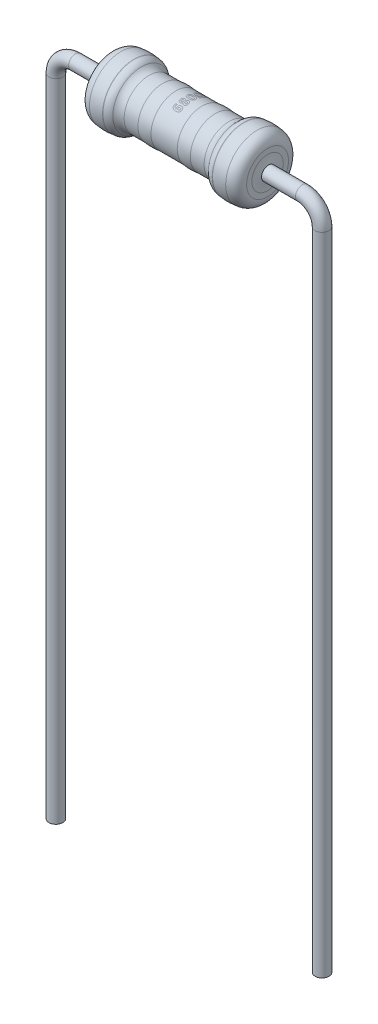
SolidWorks part; units mm, degrees
material "Plain Carbon Steel"
ref_plane "Front Plane" through (0, 0, 0) normal (0, 0, 1) x (1, 0, 0)
ref_plane "Top Plane" through (0, 0, 0) normal (0, 1, 0) x (1, 0, 0)
ref_plane "Right Plane" through (0, 0, 0) normal (1, 0, 0) x (0, 0, -1)
sketch "Sketch1" plane through (0, 0, 0) normal (0, 0, 1) x (1, 0, 0)
  line L0 (-4.33, 0) -> (4.33, 0)
  line L1 (-5.08, -0.75) -> (-5.08, -25.4)
  line L2 (5.08, -0.75) -> (5.08, -25.4)
  line L3 (-5.08, -25.4) -> (5.08, -25.4) construction
  line L4 (0, 0) -> (0, -25.4) construction
  arc A0 (-4.33, 0) -> (-5.08, -0.75) centre (-4.33, -0.75) ccw
  arc A1 (4.33, 0) -> (5.08, -0.75) centre (4.33, -0.75) cw
  dimension "D2" = 0.75
  dimension "D1" = 10.16
  dimension "D3" = 25.4
ref_plane "Plane1" through (-5.08, -25.4, 0) normal (0, -1, 0) x (-1, 0, 0)
sketch "Sketch2" plane through (-5.08, -25.4, 0) normal (0, -1, 0) x (-1, 0, 0)
  circle A0 centre (0, 0) radius 0.265
  dimension "D1" = 0.53
sweep "Sweep1" add profiles "Sketch2" path "Sketch1"
sketch "Sketch3" plane through (0, 0, 0) normal (0, 0, 1) x (1, 0, 0)
  line L0 (-3, 0) -> (3, 0)
  line L5 (-3, 0) -> (-3, 1.2)
  line L6 (3, 0) -> (3, 1.2)
  line L7 (-3, 1.2) -> (-1.75, 1.2)
  line L8 (3, 1.2) -> (1.75, 1.2)
  line L9 (-1.75, 1.2) -> (-1.75, 0.95)
  line L10 (-1.75, 0.95) -> (1.75, 0.95)
  line L11 (1.75, 0.95) -> (1.75, 1.2)
  line L12 (0, 0) -> (0, 0.95) construction
  dimension "D1" = 6
  dimension "D2" = 1.2
  dimension "D3" = 3.5
  dimension "D4" = 0.95
  dimension "D5" = 0.25
revolve "Revolve1" add sketch "Sketch3" angle 360 about L0
fillet "Fillet-1" radius 0.35 2 edges at (1.75, 0, 1.2) (-1.75, 0, 1.2)
fillet "Fillet-2" radius 0.4 4 edges at (3, 0, 1.2) (-3, 0, 1.2) (1.75, 0, 0.95) (-1.75, 0, 0.95)
sketch "Sketch5" plane through (0, 0, 0) normal (0, 0, 1) x (1, 0, 0)
  line L16 (-3, 0) -> (3, 0) construction
  line L17 (-2.6, 1.2) -> (-2.1, 1.2) construction
  line L18 (-2.6, 1.2) -> (-2.6, 0)
  line L19 (-2.6, 0) -> (-2.1, 0)
  line L20 (-2.1, 1.2) -> (-2.1, 0)
  line L21 (-1.75, 0.95) -> (1.75, 0.95) construction
  line L22 (2.6, 1.2) -> (2.1, 1.2) construction
  line L23 (2.6, 1.2) -> (2.6, 0)
  line L24 (2.6, 0) -> (2.1, 0)
  line L25 (2.1, 1.2) -> (2.1, 0)
  line L26 (-0.5, 0.95) -> (-1, 0.95) construction
  line L27 (-0.5, 0.95) -> (-0.5, 0)
  line L28 (-0.5, 0) -> (-1, 0)
  line L29 (-1, 0.95) -> (-1, 0)
  line L30 (-2.35, 1.2) -> (-2.35, 1.22) construction
  line L31 (1, 0.95) -> (0.5, 0.95) construction
  line L32 (1, 0.95) -> (1, 0)
  line L33 (1, 0) -> (0.5, 0)
  line L34 (0.5, 0.95) -> (0.5, 0)
  line L35 (-0.75, 0.95) -> (-0.75, 0.97) construction
  line L36 (0.75, 0.95) -> (0.75, 0.97) construction
  line L37 (2.35, 1.2) -> (2.35, 1.22) construction
  line L48 (-3, 0) -> (-3, 0.6)
  line L49 (-3, 0) -> (-3, 1.2) construction
  line L50 (-3, 0) -> (-3.05, 0)
  line L51 (-3.05, 0) -> (-3.05, 0.2)
  line L52 (3, 0) -> (3.05, 0)
  line L53 (3.05, 0) -> (3.05, 0.2)
  line L54 (3, 0) -> (3, 0.6)
  line L55 (3, 0) -> (3, 1.2) construction
  arc A0 (-2.6, 1.2) -> (-2.1, 1.2) centre (-2.35, -0.3525) cw
  arc A1 (-1, 0.95) -> (-0.5, 0.95) centre (-0.75, -0.6025) cw
  arc A2 (0.5, 0.95) -> (1, 0.95) centre (0.75, -0.6025) cw
  arc A3 (2.1, 1.2) -> (2.6, 1.2) centre (2.35, -0.3525) cw
  arc A6 (-3, 0.6) -> (-3.05, 0.2) centre (-4.625, 0.6) cw
  arc A7 (3.05, 0.2) -> (3, 0.6) centre (4.625, 0.6) cw
  dimension "D4" = 0.02
  dimension "D5" = 0.05
  dimension "D7" = 0.6
  dimension "D1" = 0.5
  dimension "D2" = 0.5
  dimension "D3" = 0.5
  dimension "D6" = 0.2
revolve "Revolve3" add sketch "Sketch5" angle 360 about L19
ref_plane "Plane2" through (0, 2, 0) normal (0, 1, 0) x (1, 0, 0)
sketch "Sketch6" plane through (0, 2, 0) normal (0, 1, 0) x (1, 0, 0)
  line L0 (0, 0) -> (0.15, 0) construction
  line L1 (0.15, 0.95) -> (0.15, -0.95) construction
  line L2 (0.5, 0.95) -> (-0.5, 0.95) construction
  text T0 "680Ω" font "Calibri" height 0.3
  dimension "D1" = 0.15
wrap "Wrap1" sketch "Sketch6" wrap type scribe source sketch "Sketch6" face at (-0.5, -0.95, 0)
